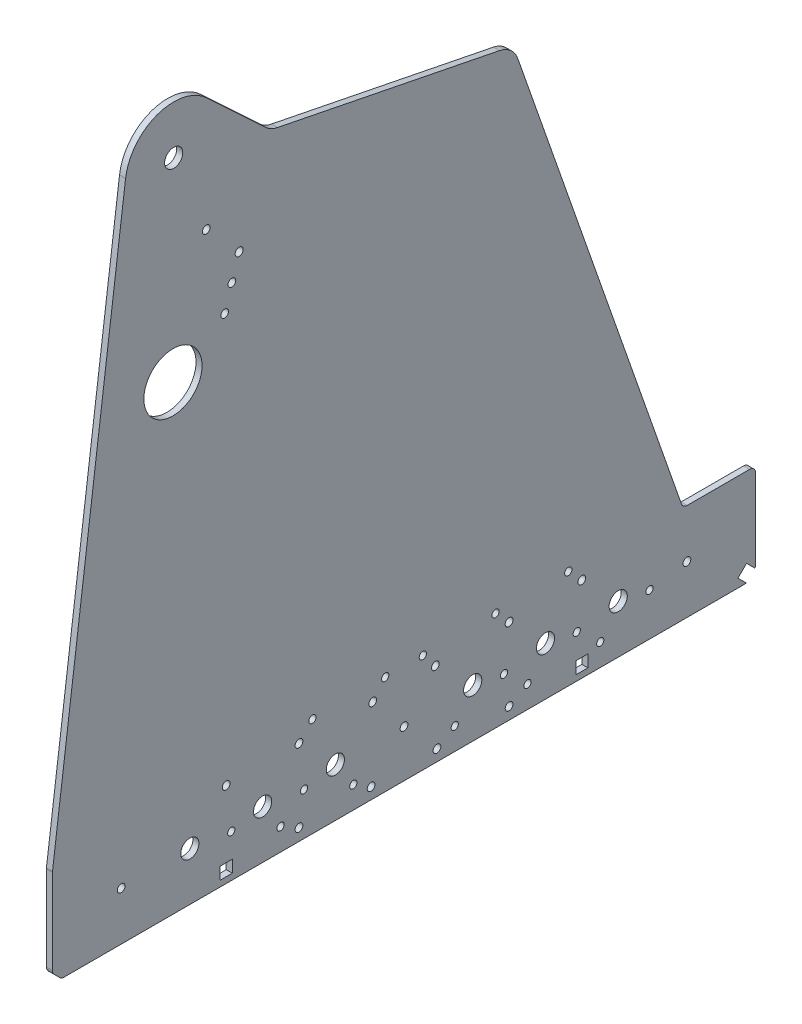
SolidWorks part; units mm, degrees
ref_plane "Front Plane" through (0, 0, 0) normal (0, 0, 1) x (1, 0, 0)
ref_plane "Top Plane" through (0, 0, 0) normal (0, 1, 0) x (1, 0, 0)
ref_plane "Right Plane" through (0, 0, 0) normal (1, 0, 0) x (0, 0, -1)
sketch "Sketch1" plane through (0, 0, 0) normal (1, 0, 0) x (0, 0, -1)
  line L0 (-184.15, -24.6062) -> (184.15, -24.6062)
  line L1 (184.15, -24.6062) -> (184.15, 26.1938)
  line L2 (184.15, 26.1938) -> (146.05, 26.1937)
  line L3 (146.05, 26.1937) -> (57.15, 280.1938)
  line L5 (-145.839, 321.5609) -> (-184.15, 26.1938)
  line L6 (-184.15, 26.1938) -> (-184.15, -24.6062)
  line L7 (-184.15, 350.0437) -> (184.15, 350.0437) construction
  line L8 (57.15, 280.1938) -> (-69.85, 305.5938)
  line L9 (-69.85, 305.5938) -> (-103.3099, 336.854)
  arc A0 (-103.3099, 336.854) -> (-145.839, 321.5609) centre (-120.65, 318.2937) ccw
  point P8 (0, -24.6062)
  dimension "D1" = 368.3
  dimension "D7" = 25.4
  dimension "D2" = 50.8
  dimension "D3" = 38.1
  dimension "D4" = 24.6062
  dimension "D5" = 374.65
  dimension "D6" = 304.8
  dimension "D8" = 342.9
  dimension "D9" = 127
  dimension "D10" = 304.8
  dimension "D11" = 25.4
  dimension "D12" = 127
extrude "Boss-Extrude1" add sketch "Sketch1" along normal blind 3.175
chamfer "Chamfer1" distance 4.7625 angle 45 2 edges at (1.5875, -24.6062, 184.15) (1.5875, -24.6062, -184.15)
fillet "Fillet1" radius 12.7 2 edges at (1.5875, 305.5938, 69.85) (1.5875, 280.1938, -57.15)
fillet "Fillet2" radius 3.175 3 edges at (1.5875, 26.1938, 184.15) (1.5875, 26.1938, -184.15) (1.5875, 26.1937, -146.05)
fillet "Fillet3" radius 3.175 4 edges at (1.5875, -19.8438, -184.15) (1.5875, -24.6062, -179.3875) (1.5875, -19.8437, 184.15) (1.5875, -24.6062, 179.3875)
sketch "Sketch16" plane through (3.175, 0, 0) normal (1, 0, 0) x (0, 0, -1)
  circle A0 centre (112.1746, 0.7937) radius 4.7625
  circle A1 centre (74.0746, 0.7937) radius 4.7625
  circle A2 centre (35.9746, 0.7937) radius 4.7625
  circle A3 centre (-35.9746, 0.7938) radius 4.7625
  circle A4 centre (-74.0746, 0.7938) radius 4.7625
  circle A5 centre (-112.1746, 0.7937) radius 4.7625
  dimension "D1" = 9.525
  dimension "D2" = 9.525
extrude "Cut-Extrude1" cut sketch "Sketch16" against normal up to next
sketch "Sketch25" plane through (3.175, 0, 0) normal (1, 0, 0) x (0, 0, -1)
  circle A0 centre (102.7672, -13.0003) radius 1.905 construction
  circle A1 centre (86.0486, 27.3622) radius 1.905 construction
  circle A2 centre (128.5804, -2.3081) radius 1.905 construction
  circle A3 centre (102.7672, -13.0003) radius 1.905
  circle A4 centre (86.0486, 27.3622) radius 1.905
  circle A5 centre (128.5804, -2.3081) radius 1.905
  circle A6 centre (64.6672, -13.0003) radius 1.905 construction
  circle A8 centre (-9.8486, 27.3622) radius 1.905 construction
  circle A10 centre (-47.9486, 27.3622) radius 1.905 construction
  circle A11 centre (-90.4804, -2.3081) radius 1.905 construction
  circle A12 centre (-64.6672, -13.0003) radius 1.905 construction
  circle A14 centre (-52.3804, -2.3081) radius 1.905 construction
  circle A15 centre (-26.5672, -13.0003) radius 1.905 construction
  circle A16 centre (9.8486, 27.3622) radius 1.905 construction
  circle A17 centre (26.5672, -13.0003) radius 1.905 construction
  circle A18 centre (47.9486, 27.3622) radius 1.905 construction
  circle A19 centre (52.3804, -2.3081) radius 1.905 construction
  circle A20 centre (90.4804, -2.3081) radius 1.905 construction
  circle A21 centre (-9.8486, 27.3622) radius 1.905
  circle A23 centre (-47.9486, 27.3622) radius 1.905
  circle A24 centre (-90.4804, -2.3081) radius 1.905
  circle A25 centre (-64.6672, -13.0003) radius 1.905
  circle A27 centre (-52.3804, -2.3081) radius 1.905
  circle A28 centre (-26.5672, -13.0003) radius 1.905
  circle A29 centre (9.8486, 27.3622) radius 1.905
  circle A30 centre (26.5672, -13.0003) radius 1.905
  circle A31 centre (47.9486, 27.3622) radius 1.905
  circle A32 centre (64.6672, -13.0003) radius 1.905
  circle A33 centre (52.3804, -2.3081) radius 1.905
  circle A34 centre (90.4804, -2.3081) radius 1.905
extrude "Cut-Extrude4" cut sketch "Sketch25" against normal up to next
sketch "Sketch23" plane through (3.175, 0, 0) normal (1, 0, 0) x (0, 0, -1)
  point P0 (-55.0246, -18.3223)
  point P3 (-55.0246, 19.9098)
  point P6 (-93.1246, 19.9098)
  point P9 (-17.2515, -18.6426)
  point P12 (-16.4124, 19.3854)
  point P15 (16.4124, 19.3854)
  point P18 (17.2515, -18.6426)
  point P21 (55.0246, -18.3223)
  point P27 (93.1246, 19.9098)
  point P30 (55.0246, 19.9098)
hole_wizard "#8 (0.16) Diameter Hole1" positions "Sketch23" profile "Sketch24" hole size "#8" standard "ANSI Inch" end condition up to next
sketch "Sketch24" plane through (3.175, -18.3223, 55.0246) normal (0, 1, 0) x (0, 0, -1)
  line L0 (0, 0) -> (0, 3.175)
  line L1 (0, 3.175) -> (2.032, 3.175)
  line L2 (2.032, 3.175) -> (2.032, 0)
  line L5 (2.032, 0) -> (0, 0)
  line L11 (0, -6.35) -> (0, 107.95) construction
  dimension "Thru Hole Dia." = 4.064
  dimension "Thru Hole Depth" = 3.175
sketch "Sketch22" plane through (3.175, 0, 0) normal (1, 0, 0) x (0, 0, -1)
  line L0 (-96.2996, -15.1473) -> (-89.9496, -15.1473) construction
  line L1 (-96.2996, -15.1473) -> (-89.9496, -15.1473)
  line L2 (-96.2996, -15.1473) -> (-96.2996, -21.4973)
  line L3 (-96.2996, -21.4973) -> (-89.9496, -21.4973)
  line L4 (-89.9496, -15.1473) -> (-89.9496, -21.4973)
  line L5 (-96.2996, -15.1473) -> (-89.9496, -21.4973) construction
  line L6 (-96.2996, -21.4973) -> (-89.9496, -15.1473) construction
  line L7 (-89.9496, -15.1473) -> (-89.9496, -19.8734) construction
  line L77 (179.3875, -24.6062) -> (183.8776, -20.1161)
  line L78 (179.3875, -24.6062) -> (174.8974, -20.1161)
  line L79 (183.8776, -20.1161) -> (179.3875, -15.626)
  line L80 (174.8974, -20.1161) -> (179.3875, -15.626)
  line L81 (180.3174, -23.6763) -> (183.2201, -20.7737) construction
  line L82 (-178.0724, -24.6062) -> (178.0724, -24.6062) construction
  line L84 (89.9496, -21.4973) -> (96.2996, -21.4973)
  line L85 (89.9496, -21.4973) -> (89.9496, -15.1473)
  line L86 (89.9496, -15.1473) -> (96.2996, -15.1473)
  line L87 (96.2996, -21.4973) -> (96.2996, -15.1473)
  line L88 (89.9496, -21.4973) -> (96.2996, -15.1473) construction
  line L89 (89.9496, -15.1473) -> (96.2996, -21.4973) construction
  point P0 (-93.1246, -18.3223)
  point P19 (93.1246, -18.3223)
  dimension "D1" = 6.35
  dimension "D2" = 6.35
extrude "Cut-Extrude3" cut sketch "Sketch22" against normal up to next
sketch "Sketch21" plane through (3.175, 0, 0) normal (1, 0, 0) x (0, 0, -1)
  circle A0 centre (-148.1579, 0.7937) radius 2.032
  circle A2 centre (0, 0) radius 2.032
  circle A3 centre (148.1579, 0.7938) radius 2.032
  dimension "D1" = 4.064
extrude "Cut-Extrude2" cut sketch "Sketch21" against normal up to next
sketch "Sketch26" plane through (3.175, 0, 0) normal (1, 0, 0) x (0, 0, -1)
  line L0 (-145.839, 321.5609) -> (-184.1236, 26.3971) construction
  line L1 (-178.0724, -24.6062) -> (178.0724, -24.6062) construction
  circle A0 centre (-121.0218, 216.6937) radius 15.24
  dimension "D1" = 30.48
  dimension "D2" = 38.1
  dimension "D3" = 241.3
extrude "Cut-Extrude5" cut sketch "Sketch26" against normal through all
sketch "Sketch27" plane through (3.175, 0, 0) normal (1, 0, 0) x (0, 0, -1)
  circle A0 centre (-120.65, 318.2937) radius 4.7625
  dimension "D1" = 9.525
extrude "Cut-Extrude6" cut sketch "Sketch27" against normal through all
sketch "Sketch28" plane through (3.175, 0, 0) normal (1, 0, 0) x (0, 0, -1)
  line L0 (-120.65, 318.2937) -> (-103.5612, 277.2599) construction
  line L1 (-103.5612, 277.2599) -> (-86.3654, 258.566) construction
  line L2 (-86.3654, 258.566) -> (-90.1612, 246.4465) construction
  line L3 (-90.1612, 246.4465) -> (-93.9569, 234.327) construction
  line L4 (-145.839, 321.5609) -> (-184.1236, 26.3971) construction
  circle A0 centre (-93.9569, 234.327) radius 2.032
  circle A1 centre (-90.1612, 246.4465) radius 2.032
  circle A2 centre (-86.3654, 258.566) radius 2.0955
  circle A3 centre (-103.5612, 277.2599) radius 2.032
  dimension "D4" = 4.064
  dimension "D5" = 4.191
  dimension "D6" = 4.064
  dimension "D1" = 25.4
  dimension "D2" = 44.45
  dimension "D3" = 12.7
  dimension "D7" = 30
  dimension "D8" = 120
  dimension "D9" = 160
extrude "Cut-Extrude7" cut sketch "Sketch28" against normal through all
